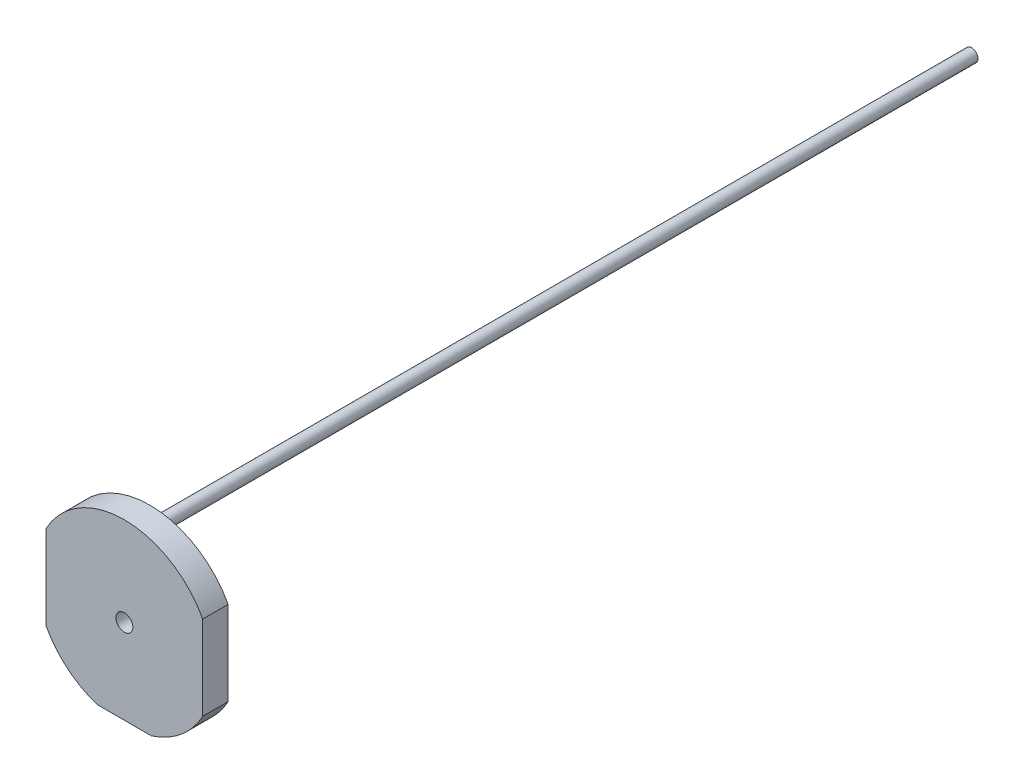
SolidWorks part; units mm, degrees
ref_plane "前视基准面" through (0, 0, 0) normal (0, 0, 1) x (1, 0, 0)
ref_plane "上视基准面" through (0, 0, 0) normal (0, 1, 0) x (1, 0, 0)
ref_plane "右视基准面" through (0, 0, 0) normal (1, 0, 0) x (0, 0, -1)
other "Configuration Table"
sketch "草图4" plane through (0, 0, 0) normal (0, 0, 1) x (1, 0, 0)
  line L0 (-18.5, 9.9373) -> (-18.5, -9.9373)
  line L1 (18.5, 9.9373) -> (18.5, -9.9373)
  line L2 (-6.4031, -20) -> (6.4031, -20)
  arc A0 (-18.5, -9.9373) -> (-6.4031, -20) centre (0, 0) ccw
  arc A1 (18.5, 9.9373) -> (-18.5, 9.9373) centre (0, 0) ccw
  arc A2 (6.4031, -20) -> (18.5, -9.9373) centre (0, 0) ccw
  circle A3 centre (0, 0) radius 2
  circle A4 centre (0, 16) radius 1.5
  dimension "D2" = 21
  dimension "D4" = 3
  dimension "D5" = 4
  dimension "D1" = 20
  dimension "D3" = 37
  dimension "D6" = 16
extrude "凸台-拉伸1" add sketch "草图4" against normal blind 6
extrude "凸台-拉伸2" add sketch "草图4<2>" against normal blind 200 contours A4 region at (0, 16, 0)
sketch "草图4<2>" plane through (0, 0, 0) normal (0, 0, 1) x (1, 0, 0) same geometry as "草图4"
